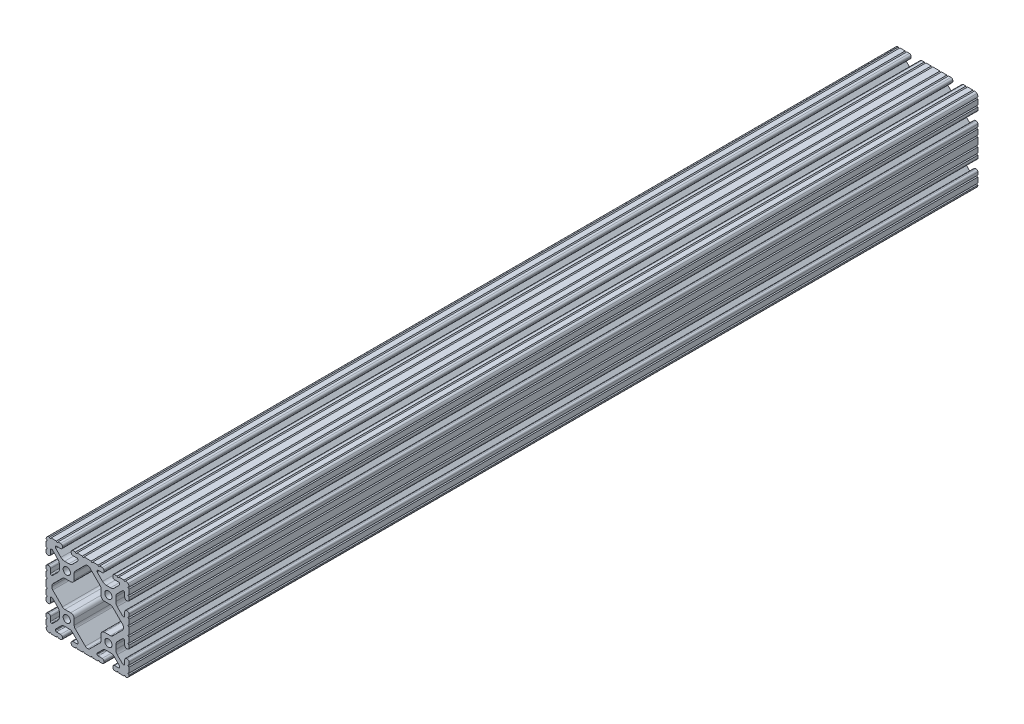
SolidWorks part; units mm, degrees
ref_plane "Front Plane" through (0, 0, 0) normal (0, 0, 1) x (1, 0, 0)
ref_plane "Top Plane" through (0, 0, 0) normal (0, 1, 0) x (1, 0, 0)
ref_plane "Right Plane" through (0, 0, 0) normal (1, 0, 0) x (0, 0, -1)
sketch "Sketch1" plane through (0, 0, 0) normal (0, 0, 1) x (1, 0, 0)
  line L0 (0, 38.1) -> (0, -38.1) construction
  line L1 (-38.1, -38.1) -> (38.1, -38.1) construction
  line L2 (-38.1, -38.1) -> (-38.1, 38.1) construction
  line L3 (-38.1, 38.1) -> (38.1, 38.1) construction
  line L4 (38.1, -38.1) -> (38.1, 38.1) construction
  line L5 (0, 38.1) -> (0, -38.1) construction
  line L6 (-38.1, 0) -> (38.1, 0) construction
  line L7 (-19.05, 19.05) -> (19.05, 19.05) construction
  line L8 (-19.05, 19.05) -> (-19.05, -19.05) construction
  line L9 (-19.05, -19.05) -> (19.05, -19.05) construction
  line L10 (19.05, 19.05) -> (19.05, -19.05) construction
  line L11 (-23.114, 38.1) -> (-23.114, -38.1) construction
  line L12 (-23.114, -38.1) -> (-14.986, 38.1) construction
  line L13 (-14.986, 38.1) -> (-14.986, -38.1) construction
  circle A0 centre (19.05, 19.05) radius 3.3274
  point P0 (0, 0)
  point P9 (0, 0)
  point P12 (-19.05, 0)
  line B0 (-11.3637, -22.8433) -> (-2.0515, -32.1555)
  line B1 (-12.2936, -15.4686) -> (-12.2936, -20.5983)
  line B2 (-20.769, -12.2936) -> (-15.4686, -12.2936)
  line B3 (-31.9021, -2.4756) -> (-23.0141, -11.3637)
  line B4 (-23.0141, 11.3637) -> (-31.9021, 2.4756)
  line B5 (-15.4686, 12.2936) -> (-20.769, 12.2936)
  line B6 (-12.2936, 20.5983) -> (-12.2936, 15.4686)
  line B7 (-2.0515, 32.1555) -> (-11.3637, 22.8433)
  line B8 (11.3637, 22.8433) -> (2.0515, 32.1555)
  line B9 (12.2936, 15.4686) -> (12.2936, 20.5983)
  line B10 (20.769, 12.2936) -> (15.4686, 12.2936)
  line B11 (31.9021, 2.4756) -> (23.0141, 11.3637)
  line B12 (23.0141, -11.3637) -> (31.9021, -2.4756)
  line B13 (15.4686, -12.2936) -> (20.769, -12.2936)
  line B14 (12.2936, -20.5983) -> (12.2936, -15.4686)
  line B15 (2.0515, -32.1555) -> (11.3637, -22.8433)
  line B16 (-4.7773, 38.1) -> (-9.6053, 38.1)
  line B17 (-11.1289, 38.1) -> (-13.4112, 38.1)
  line B18 (-14.986, 36.5252) -> (-14.986, 35.6108)
  line B19 (-13.4112, 34.036) -> (-9.652, 34.036)
  line B20 (-8.763, 33.147) -> (-8.763, 32.4935)
  line B21 (-9.0234, 31.8649) -> (-13.6907, 27.1976)
  line B22 (-17.0493, 25.8064) -> (-21.0507, 25.8064)
  line B23 (-24.4093, 27.1976) -> (-29.1002, 31.8885)
  line B24 (-29.337, 32.7207) -> (-29.337, 33.147)
  line B25 (-28.448, 34.036) -> (-24.6888, 34.036)
  line B26 (-23.114, 35.6108) -> (-23.114, 36.5252)
  line B27 (-24.6888, 38.1) -> (-27.0772, 38.1)
  line B28 (-28.6011, 38.1) -> (-33.4288, 38.1)
  line B29 (-38.1, 33.373) -> (-38.1, 28.5453)
  line B30 (-38.1, 27.0238) -> (-38.1, 24.6302)
  line B31 (-36.5252, 23.0554) -> (-35.6108, 23.0554)
  line B32 (-34.036, 24.6302) -> (-34.036, 28.448)
  line B33 (-33.147, 29.337) -> (-32.6643, 29.337)
  line B34 (-32.0357, 29.0766) -> (-27.1976, 24.2385)
  line B35 (-25.8064, 20.8799) -> (-25.8064, 17.2201)
  line B36 (-27.1976, 13.8615) -> (-31.9489, 9.1101)
  line B37 (-32.7869, 8.763) -> (-33.0603, 8.763)
  line B38 (-34.036, 9.7387) -> (-34.036, 13.4698)
  line B39 (-35.6108, 15.0446) -> (-36.5252, 15.0446)
  line B40 (-38.1, 13.4698) -> (-38.1, 11.075)
  line B41 (-38.1, 9.552) -> (-38.1, 4.7238)
  line B42 (-38.1, 3.2007) -> (-38.1, -3.2007)
  line B43 (-38.1, -4.7238) -> (-38.1, -9.552)
  line B44 (-38.1, -11.075) -> (-38.1, -13.4698)
  line B45 (-36.5252, -15.0446) -> (-35.6108, -15.0446)
  line B46 (-34.036, -13.4698) -> (-34.036, -9.7387)
  line B47 (-33.0603, -8.763) -> (-32.7869, -8.763)
  line B48 (-31.9489, -9.1101) -> (-27.1976, -13.8615)
  line B49 (-25.8064, -17.2201) -> (-25.8064, -20.8799)
  line B50 (-27.1976, -24.2385) -> (-32.0357, -29.0766)
  line B51 (-32.6643, -29.337) -> (-33.147, -29.337)
  line B52 (-34.036, -28.448) -> (-34.036, -24.6302)
  line B53 (-35.6108, -23.0554) -> (-36.5252, -23.0554)
  line B54 (-38.1, -24.6302) -> (-38.1, -27.0238)
  line B55 (-38.1, -28.5453) -> (-38.1, -33.373)
  line B56 (-33.4288, -38.1) -> (-28.6011, -38.1)
  line B57 (-27.0772, -38.1) -> (-24.6888, -38.1)
  line B58 (-23.114, -36.5252) -> (-23.114, -35.6108)
  line B59 (-24.6888, -34.036) -> (-28.448, -34.036)
  line B60 (-29.337, -33.147) -> (-29.337, -32.7207)
  line B61 (-29.1002, -31.8885) -> (-24.4093, -27.1976)
  line B62 (-21.0507, -25.8064) -> (-17.0493, -25.8064)
  line B63 (-13.6907, -27.1976) -> (-9.0234, -31.8649)
  line B64 (-8.763, -32.4935) -> (-8.763, -33.147)
  line B65 (-9.652, -34.036) -> (-13.4112, -34.036)
  line B66 (-14.986, -35.6108) -> (-14.986, -36.5252)
  line B67 (-13.4112, -38.1) -> (-11.1289, -38.1)
  line B68 (-9.6053, -38.1) -> (-4.7773, -38.1)
  line B69 (-3.2537, -38.1) -> (3.2537, -38.1)
  line B70 (4.7773, -38.1) -> (9.6053, -38.1)
  line B71 (11.1289, -38.1) -> (13.4112, -38.1)
  line B72 (14.986, -36.5252) -> (14.986, -35.6108)
  line B73 (13.4112, -34.036) -> (9.652, -34.036)
  line B74 (8.763, -33.147) -> (8.763, -32.4935)
  line B75 (9.0234, -31.8649) -> (13.6907, -27.1976)
  line B76 (17.0493, -25.8064) -> (21.0507, -25.8064)
  line B77 (24.4093, -27.1976) -> (29.1002, -31.8885)
  line B78 (29.337, -32.7207) -> (29.337, -33.147)
  line B79 (28.448, -34.036) -> (24.6888, -34.036)
  line B80 (23.114, -35.6108) -> (23.114, -36.5252)
  line B81 (24.6888, -38.1) -> (27.0772, -38.1)
  line B82 (28.6011, -38.1) -> (33.4288, -38.1)
  line B83 (38.1, -33.373) -> (38.1, -28.5453)
  line B84 (38.1, -27.0238) -> (38.1, -24.6302)
  line B85 (36.5252, -23.0554) -> (35.6108, -23.0554)
  line B86 (34.036, -24.6302) -> (34.036, -28.448)
  line B87 (33.147, -29.337) -> (32.6643, -29.337)
  line B88 (32.0357, -29.0766) -> (27.1976, -24.2385)
  line B89 (25.8064, -20.8799) -> (25.8064, -17.2201)
  line B90 (27.1976, -13.8615) -> (31.9489, -9.1101)
  line B91 (32.7869, -8.763) -> (33.0603, -8.763)
  line B92 (34.036, -9.7387) -> (34.036, -13.4698)
  line B93 (35.6108, -15.0446) -> (36.5252, -15.0446)
  line B94 (38.1, -13.4698) -> (38.1, -11.075)
  line B95 (38.1, -9.552) -> (38.1, -4.7238)
  line B96 (38.1, -3.2007) -> (38.1, 3.2007)
  line B97 (38.1, 4.7238) -> (38.1, 9.552)
  line B98 (38.1, 11.075) -> (38.1, 13.4698)
  line B99 (36.5252, 15.0446) -> (35.6108, 15.0446)
  line B100 (34.036, 13.4698) -> (34.036, 9.7387)
  line B101 (33.0603, 8.763) -> (32.7869, 8.763)
  line B102 (31.9489, 9.1101) -> (27.1976, 13.8615)
  line B103 (25.8064, 17.2201) -> (25.8064, 20.8799)
  line B104 (27.1976, 24.2385) -> (32.0357, 29.0766)
  line B105 (32.6643, 29.337) -> (33.147, 29.337)
  line B106 (34.036, 28.448) -> (34.036, 24.6302)
  line B107 (35.6108, 23.0554) -> (36.5252, 23.0554)
  line B108 (38.1, 24.6302) -> (38.1, 27.0238)
  line B109 (38.1, 28.5453) -> (38.1, 33.373)
  line B110 (33.4288, 38.1) -> (28.6011, 38.1)
  line B111 (27.0772, 38.1) -> (24.6888, 38.1)
  line B112 (23.114, 36.5252) -> (23.114, 35.6108)
  line B113 (24.6888, 34.036) -> (28.448, 34.036)
  line B114 (29.337, 33.147) -> (29.337, 32.7207)
  line B115 (29.1002, 31.8885) -> (24.4093, 27.1976)
  line B116 (21.0507, 25.8064) -> (17.0493, 25.8064)
  line B117 (13.6907, 27.1976) -> (9.0234, 31.8649)
  line B118 (8.763, 32.4935) -> (8.763, 33.147)
  line B119 (9.652, 34.036) -> (13.4112, 34.036)
  line B120 (14.986, 35.6108) -> (14.986, 36.5252)
  line B121 (13.4112, 38.1) -> (11.1289, 38.1)
  line B122 (9.6053, 38.1) -> (4.7773, 38.1)
  line B123 (3.2537, 38.1) -> (-3.2537, 38.1)
  circle B124 centre (-19.05, 19.05) radius 3.3274
  circle B125 centre (-19.05, -19.05) radius 3.3274
  circle B126 centre (19.05, -19.05) radius 3.3274
  circle B127 centre (19.05, 19.05) radius 3.3274
  arc B128 (0, -33.011) -> (2.0515, -32.1555) centre (-0.0139, -30.09) ccw
  arc B129 (-2.0515, -32.1555) -> (0, -33.011) centre (0.0139, -30.09) ccw
  arc B130 (-12.2936, -20.5983) -> (-11.3637, -22.8433) centre (-9.1186, -20.5983) ccw
  arc B131 (-12.2936, -15.4686) -> (-15.4686, -12.2936) centre (-15.4686, -15.4686) ccw
  arc B132 (-23.0141, -11.3637) -> (-20.769, -12.2936) centre (-20.769, -9.1186) ccw
  arc B133 (-32.7287, 0) -> (-31.9021, -2.4756) centre (-29.8367, -0.4102) ccw
  arc B134 (-31.9021, 2.4756) -> (-32.7287, 0) centre (-29.8367, 0.4102) ccw
  arc B135 (-20.769, 12.2936) -> (-23.0141, 11.3637) centre (-20.769, 9.1186) ccw
  arc B136 (-15.4686, 12.2936) -> (-12.2936, 15.4686) centre (-15.4686, 15.4686) ccw
  arc B137 (-11.3637, 22.8433) -> (-12.2936, 20.5983) centre (-9.1186, 20.5983) ccw
  arc B138 (0, 33.011) -> (-2.0515, 32.1555) centre (0.0139, 30.09) ccw
  arc B139 (2.0515, 32.1555) -> (0, 33.011) centre (-0.0139, 30.09) ccw
  arc B140 (12.2936, 20.5983) -> (11.3637, 22.8433) centre (9.1186, 20.5983) ccw
  arc B141 (12.2936, 15.4686) -> (15.4686, 12.2936) centre (15.4686, 15.4686) ccw
  arc B142 (23.0141, 11.3637) -> (20.769, 12.2936) centre (20.769, 9.1186) ccw
  arc B143 (32.7287, 0) -> (31.9021, 2.4756) centre (29.8367, 0.4102) ccw
  arc B144 (31.9021, -2.4756) -> (32.7287, 0) centre (29.8367, -0.4102) ccw
  arc B145 (20.769, -12.2936) -> (23.0141, -11.3637) centre (20.769, -9.1186) ccw
  arc B146 (15.4686, -12.2936) -> (12.2936, -15.4686) centre (15.4686, -15.4686) ccw
  arc B147 (11.3637, -22.8433) -> (12.2936, -20.5983) centre (9.1186, -20.5983) ccw
  arc B148 (-4.7773, 38.1) -> (-3.2537, 38.1) centre (-4.0155, 38.0824) ccw
  arc B149 (-11.1289, 38.1) -> (-9.6053, 38.1) centre (-10.3671, 38.0824) ccw
  arc B150 (-13.4112, 38.1) -> (-14.986, 36.5252) centre (-13.4112, 36.5252) ccw
  arc B151 (-14.986, 35.6108) -> (-13.4112, 34.036) centre (-13.4112, 35.6108) ccw
  arc B152 (-8.763, 33.147) -> (-9.652, 34.036) centre (-9.652, 33.147) ccw
  arc B153 (-9.0234, 31.8649) -> (-8.763, 32.4935) centre (-9.652, 32.4935) ccw
  arc B154 (-17.0493, 25.8064) -> (-13.6907, 27.1976) centre (-17.0493, 30.5562) ccw
  arc B155 (-24.4093, 27.1976) -> (-21.0507, 25.8064) centre (-21.0507, 30.5562) ccw
  arc B156 (-29.337, 32.7207) -> (-29.1002, 31.8885) centre (-28.4716, 32.5172) ccw
  arc B157 (-28.448, 34.036) -> (-29.337, 33.147) centre (-28.448, 33.147) ccw
  arc B158 (-24.6888, 34.036) -> (-23.114, 35.6108) centre (-24.6888, 35.6108) ccw
  arc B159 (-23.114, 36.5252) -> (-24.6888, 38.1) centre (-24.6888, 36.5252) ccw
  arc B160 (-28.6011, 38.1) -> (-27.0772, 38.1) centre (-27.8392, 38.0824) ccw
  arc B161 (-34.9527, 38.1) -> (-33.4288, 38.1) centre (-34.1907, 38.0824) ccw
  arc B162 (-34.9527, 38.1) -> (-37.0861, 37.1826) centre (-34.8521, 34.9266) ccw
  arc B163 (-37.0861, 37.1826) -> (-38.1, 34.8455) centre (-34.925, 34.8566) ccw
  arc B164 (-38.1, 33.373) -> (-38.1, 34.8455) centre (-37.9035, 34.1092) ccw
  arc B165 (-38.1, 27.0238) -> (-38.1, 28.5453) centre (-37.9035, 27.7845) ccw
  arc B166 (-38.1, 24.6302) -> (-36.5252, 23.0554) centre (-36.5252, 24.6302) ccw
  arc B167 (-35.6108, 23.0554) -> (-34.036, 24.6302) centre (-35.6108, 24.6302) ccw
  arc B168 (-33.147, 29.337) -> (-34.036, 28.448) centre (-33.147, 28.448) ccw
  arc B169 (-32.0357, 29.0766) -> (-32.6643, 29.337) centre (-32.6643, 28.448) ccw
  arc B170 (-25.8064, 20.8799) -> (-27.1976, 24.2385) centre (-30.5562, 20.8799) ccw
  arc B171 (-27.1976, 13.8615) -> (-25.8064, 17.2201) centre (-30.5562, 17.2201) ccw
  arc B172 (-32.7869, 8.763) -> (-31.9489, 9.1101) centre (-32.7869, 9.9481) ccw
  arc B173 (-34.036, 9.7387) -> (-33.0603, 8.763) centre (-33.0603, 9.7387) ccw
  arc B174 (-34.036, 13.4698) -> (-35.6108, 15.0446) centre (-35.6108, 13.4698) ccw
  arc B175 (-36.5252, 15.0446) -> (-38.1, 13.4698) centre (-36.5252, 13.4698) ccw
  arc B176 (-38.1, 9.552) -> (-38.1, 11.075) centre (-37.9035, 10.3135) ccw
  arc B177 (-38.1, 3.2007) -> (-38.1, 4.7238) centre (-37.9035, 3.9622) ccw
  arc B178 (-38.1, -4.7238) -> (-38.1, -3.2007) centre (-37.9035, -3.9622) ccw
  arc B179 (-38.1, -11.075) -> (-38.1, -9.552) centre (-37.9035, -10.3135) ccw
  arc B180 (-38.1, -13.4698) -> (-36.5252, -15.0446) centre (-36.5252, -13.4698) ccw
  arc B181 (-35.6108, -15.0446) -> (-34.036, -13.4698) centre (-35.6108, -13.4698) ccw
  arc B182 (-33.0603, -8.763) -> (-34.036, -9.7387) centre (-33.0603, -9.7387) ccw
  arc B183 (-31.9489, -9.1101) -> (-32.7869, -8.763) centre (-32.7869, -9.9481) ccw
  arc B184 (-25.8064, -17.2201) -> (-27.1976, -13.8615) centre (-30.5562, -17.2201) ccw
  arc B185 (-27.1976, -24.2385) -> (-25.8064, -20.8799) centre (-30.5562, -20.8799) ccw
  arc B186 (-32.6643, -29.337) -> (-32.0357, -29.0766) centre (-32.6643, -28.448) ccw
  arc B187 (-34.036, -28.448) -> (-33.147, -29.337) centre (-33.147, -28.448) ccw
  arc B188 (-34.036, -24.6302) -> (-35.6108, -23.0554) centre (-35.6108, -24.6302) ccw
  arc B189 (-36.5252, -23.0554) -> (-38.1, -24.6302) centre (-36.5252, -24.6302) ccw
  arc B190 (-38.1, -28.5453) -> (-38.1, -27.0238) centre (-37.9035, -27.7845) ccw
  arc B191 (-38.1, -34.8455) -> (-38.1, -33.373) centre (-37.9035, -34.1092) ccw
  arc B192 (-38.1, -34.8455) -> (-37.0861, -37.1826) centre (-34.925, -34.8566) ccw
  arc B193 (-37.0861, -37.1826) -> (-34.9527, -38.1) centre (-34.8521, -34.9266) ccw
  arc B194 (-33.4288, -38.1) -> (-34.9527, -38.1) centre (-34.1907, -38.0824) ccw
  arc B195 (-27.0772, -38.1) -> (-28.6011, -38.1) centre (-27.8392, -38.0824) ccw
  arc B196 (-24.6888, -38.1) -> (-23.114, -36.5252) centre (-24.6888, -36.5252) ccw
  arc B197 (-23.114, -35.6108) -> (-24.6888, -34.036) centre (-24.6888, -35.6108) ccw
  arc B198 (-29.337, -33.147) -> (-28.448, -34.036) centre (-28.448, -33.147) ccw
  arc B199 (-29.1002, -31.8885) -> (-29.337, -32.7207) centre (-28.4716, -32.5172) ccw
  arc B200 (-21.0507, -25.8064) -> (-24.4093, -27.1976) centre (-21.0507, -30.5562) ccw
  arc B201 (-13.6907, -27.1976) -> (-17.0493, -25.8064) centre (-17.0493, -30.5562) ccw
  arc B202 (-8.763, -32.4935) -> (-9.0234, -31.8649) centre (-9.652, -32.4935) ccw
  arc B203 (-9.652, -34.036) -> (-8.763, -33.147) centre (-9.652, -33.147) ccw
  arc B204 (-13.4112, -34.036) -> (-14.986, -35.6108) centre (-13.4112, -35.6108) ccw
  arc B205 (-14.986, -36.5252) -> (-13.4112, -38.1) centre (-13.4112, -36.5252) ccw
  arc B206 (-9.6053, -38.1) -> (-11.1289, -38.1) centre (-10.3671, -38.0824) ccw
  arc B207 (-3.2537, -38.1) -> (-4.7773, -38.1) centre (-4.0155, -38.0824) ccw
  arc B208 (4.7773, -38.1) -> (3.2537, -38.1) centre (4.0155, -38.0824) ccw
  arc B209 (11.1289, -38.1) -> (9.6053, -38.1) centre (10.3671, -38.0824) ccw
  arc B210 (13.4112, -38.1) -> (14.986, -36.5252) centre (13.4112, -36.5252) ccw
  arc B211 (14.986, -35.6108) -> (13.4112, -34.036) centre (13.4112, -35.6108) ccw
  arc B212 (8.763, -33.147) -> (9.652, -34.036) centre (9.652, -33.147) ccw
  arc B213 (9.0234, -31.8649) -> (8.763, -32.4935) centre (9.652, -32.4935) ccw
  arc B214 (17.0493, -25.8064) -> (13.6907, -27.1976) centre (17.0493, -30.5562) ccw
  arc B215 (24.4093, -27.1976) -> (21.0507, -25.8064) centre (21.0507, -30.5562) ccw
  arc B216 (29.337, -32.7207) -> (29.1002, -31.8885) centre (28.4716, -32.5172) ccw
  arc B217 (28.448, -34.036) -> (29.337, -33.147) centre (28.448, -33.147) ccw
  arc B218 (24.6888, -34.036) -> (23.114, -35.6108) centre (24.6888, -35.6108) ccw
  arc B219 (23.114, -36.5252) -> (24.6888, -38.1) centre (24.6888, -36.5252) ccw
  arc B220 (28.6011, -38.1) -> (27.0772, -38.1) centre (27.8392, -38.0824) ccw
  arc B221 (34.9527, -38.1) -> (33.4288, -38.1) centre (34.1907, -38.0824) ccw
  arc B222 (34.9527, -38.1) -> (37.0861, -37.1826) centre (34.8521, -34.9266) ccw
  arc B223 (37.0861, -37.1826) -> (38.1, -34.8455) centre (34.925, -34.8566) ccw
  arc B224 (38.1, -33.373) -> (38.1, -34.8455) centre (37.9035, -34.1092) ccw
  arc B225 (38.1, -27.0238) -> (38.1, -28.5453) centre (37.9035, -27.7845) ccw
  arc B226 (38.1, -24.6302) -> (36.5252, -23.0554) centre (36.5252, -24.6302) ccw
  arc B227 (35.6108, -23.0554) -> (34.036, -24.6302) centre (35.6108, -24.6302) ccw
  arc B228 (33.147, -29.337) -> (34.036, -28.448) centre (33.147, -28.448) ccw
  arc B229 (32.0357, -29.0766) -> (32.6643, -29.337) centre (32.6643, -28.448) ccw
  arc B230 (25.8064, -20.8799) -> (27.1976, -24.2385) centre (30.5562, -20.8799) ccw
  arc B231 (27.1976, -13.8615) -> (25.8064, -17.2201) centre (30.5562, -17.2201) ccw
  arc B232 (32.7869, -8.763) -> (31.9489, -9.1101) centre (32.7869, -9.9481) ccw
  arc B233 (34.036, -9.7387) -> (33.0603, -8.763) centre (33.0603, -9.7387) ccw
  arc B234 (34.036, -13.4698) -> (35.6108, -15.0446) centre (35.6108, -13.4698) ccw
  arc B235 (36.5252, -15.0446) -> (38.1, -13.4698) centre (36.5252, -13.4698) ccw
  arc B236 (38.1, -9.552) -> (38.1, -11.075) centre (37.9035, -10.3135) ccw
  arc B237 (38.1, -3.2007) -> (38.1, -4.7238) centre (37.9035, -3.9622) ccw
  arc B238 (38.1, 4.7238) -> (38.1, 3.2007) centre (37.9035, 3.9622) ccw
  arc B239 (38.1, 11.075) -> (38.1, 9.552) centre (37.9035, 10.3135) ccw
  arc B240 (38.1, 13.4698) -> (36.5252, 15.0446) centre (36.5252, 13.4698) ccw
  arc B241 (35.6108, 15.0446) -> (34.036, 13.4698) centre (35.6108, 13.4698) ccw
  arc B242 (33.0603, 8.763) -> (34.036, 9.7387) centre (33.0603, 9.7387) ccw
  arc B243 (31.9489, 9.1101) -> (32.7869, 8.763) centre (32.7869, 9.9481) ccw
  arc B244 (25.8064, 17.2201) -> (27.1976, 13.8615) centre (30.5562, 17.2201) ccw
  arc B245 (27.1976, 24.2385) -> (25.8064, 20.8799) centre (30.5562, 20.8799) ccw
  arc B246 (32.6643, 29.337) -> (32.0357, 29.0766) centre (32.6643, 28.448) ccw
  arc B247 (34.036, 28.448) -> (33.147, 29.337) centre (33.147, 28.448) ccw
  arc B248 (34.036, 24.6302) -> (35.6108, 23.0554) centre (35.6108, 24.6302) ccw
  arc B249 (36.5252, 23.0554) -> (38.1, 24.6302) centre (36.5252, 24.6302) ccw
  arc B250 (38.1, 28.5453) -> (38.1, 27.0238) centre (37.9035, 27.7845) ccw
  arc B251 (38.1, 34.8455) -> (38.1, 33.373) centre (37.9035, 34.1092) ccw
  arc B252 (38.1, 34.8455) -> (37.0861, 37.1826) centre (34.925, 34.8566) ccw
  arc B253 (37.0861, 37.1826) -> (34.9527, 38.1) centre (34.8521, 34.9266) ccw
  arc B254 (33.4288, 38.1) -> (34.9527, 38.1) centre (34.1907, 38.0824) ccw
  arc B255 (27.0772, 38.1) -> (28.6011, 38.1) centre (27.8392, 38.0824) ccw
  arc B256 (24.6888, 38.1) -> (23.114, 36.5252) centre (24.6888, 36.5252) ccw
  arc B257 (23.114, 35.6108) -> (24.6888, 34.036) centre (24.6888, 35.6108) ccw
  arc B258 (29.337, 33.147) -> (28.448, 34.036) centre (28.448, 33.147) ccw
  arc B259 (29.1002, 31.8885) -> (29.337, 32.7207) centre (28.4716, 32.5172) ccw
  arc B260 (21.0507, 25.8064) -> (24.4093, 27.1976) centre (21.0507, 30.5562) ccw
  arc B261 (13.6907, 27.1976) -> (17.0493, 25.8064) centre (17.0493, 30.5562) ccw
  arc B262 (8.763, 32.4935) -> (9.0234, 31.8649) centre (9.652, 32.4935) ccw
  arc B263 (9.652, 34.036) -> (8.763, 33.147) centre (9.652, 33.147) ccw
  arc B264 (13.4112, 34.036) -> (14.986, 35.6108) centre (13.4112, 35.6108) ccw
  arc B265 (14.986, 36.5252) -> (13.4112, 38.1) centre (13.4112, 36.5252) ccw
  arc B266 (9.6053, 38.1) -> (11.1289, 38.1) centre (10.3671, 38.0824) ccw
  arc B267 (3.2537, 38.1) -> (4.7773, 38.1) centre (4.0155, 38.0824) ccw
  dimension "Center Hole Diameter" = 6.6548
  dimension "Rail Width" = 76.2
  dimension "Rail Height" = 76.2
  dimension "T-Slot Width" = 8.128
sketch_block_instance "Block1-1"
sketch_block "Block1"
sketch "Sketch2" plane through (0, 0, 0) normal (1, 0, 0) x (0, 0, -1)
  line L0 (-388.8, 0) -> (388.8, 0) construction
  line L1 (-388.8, 38.1) -> (-388.8, -38.1) construction
  line L2 (-388.8, -38.1) -> (388.8, -38.1) construction
  line L3 (388.8, -38.1) -> (388.8, 38.1) construction
  line L4 (-287.2, 0) -> (-287.2, 38.1) construction
  line L5 (-287.2, 38.1) -> (287.2, 38.1) construction
  line L6 (287.2, 38.1) -> (287.2, 0) construction
  point P5 (287.2, 0)
  point P10 (-287.2, 0)
  dimension "D1" = 101.6
  dimension "Length" = 777.6
  dimension "D2" = 101.6
sketch "Sketch3" plane through (0, 0, 0) normal (0, 0, 1) x (1, 0, 0)
  line L0 (-11.3637, -22.8433) -> (-2.0515, -32.1555) construction
  line L1 (-12.2936, -15.4686) -> (-12.2936, -20.5983) construction
  line L2 (-20.769, -12.2936) -> (-15.4686, -12.2936) construction
  line L3 (-31.9021, -2.4756) -> (-23.0141, -11.3637) construction
  line L4 (-23.0141, 11.3637) -> (-31.9021, 2.4756) construction
  line L5 (-15.4686, 12.2936) -> (-20.769, 12.2936) construction
  line L6 (-12.2936, 20.5983) -> (-12.2936, 15.4686) construction
  line L7 (-2.0515, 32.1555) -> (-11.3637, 22.8433) construction
  line L8 (11.3637, 22.8433) -> (2.0515, 32.1555) construction
  line L9 (12.2936, 15.4686) -> (12.2936, 20.5983) construction
  line L10 (20.769, 12.2936) -> (15.4686, 12.2936) construction
  line L11 (31.9021, 2.4756) -> (23.0141, 11.3637) construction
  line L12 (23.0141, -11.3637) -> (31.9021, -2.4756) construction
  line L13 (15.4686, -12.2936) -> (20.769, -12.2936) construction
  line L14 (12.2936, -20.5983) -> (12.2936, -15.4686) construction
  line L15 (2.0515, -32.1555) -> (11.3637, -22.8433) construction
  line L16 (34.036, 28.448) -> (34.036, 24.6302) construction
  line L17 (35.6108, 23.0554) -> (36.5252, 23.0554) construction
  line L18 (38.1, 24.6302) -> (38.1, 27.0238) construction
  line L19 (38.1, 28.5453) -> (38.1, 33.373) construction
  line L20 (33.4288, 38.1) -> (28.6011, 38.1) construction
  line L21 (27.0772, 38.1) -> (24.6888, 38.1) construction
  line L22 (23.114, 36.5252) -> (23.114, 35.6108) construction
  line L23 (24.6888, 34.036) -> (28.448, 34.036) construction
  line L24 (29.337, 33.147) -> (29.337, 32.7207) construction
  line L25 (29.1002, 31.8885) -> (24.4093, 27.1976) construction
  line L26 (21.0507, 25.8064) -> (17.0493, 25.8064) construction
  line L27 (13.6907, 27.1976) -> (9.0234, 31.8649) construction
  line L28 (8.763, 32.4935) -> (8.763, 33.147) construction
  line L29 (9.652, 34.036) -> (13.4112, 34.036) construction
  line L30 (14.986, 35.6108) -> (14.986, 36.5252) construction
  line L31 (13.4112, 38.1) -> (11.1289, 38.1) construction
  line L32 (9.6053, 38.1) -> (4.7773, 38.1) construction
  line L33 (3.2537, 38.1) -> (-3.2537, 38.1) construction
  line L34 (-4.7773, 38.1) -> (-9.6053, 38.1) construction
  line L35 (-11.1289, 38.1) -> (-13.4112, 38.1) construction
  line L36 (-14.986, 36.5252) -> (-14.986, 35.6108) construction
  line L37 (-13.4112, 34.036) -> (-9.652, 34.036) construction
  line L38 (-8.763, 33.147) -> (-8.763, 32.4935) construction
  line L39 (-9.0234, 31.8649) -> (-13.6907, 27.1976) construction
  line L40 (-17.0493, 25.8064) -> (-21.0507, 25.8064) construction
  line L41 (-24.4093, 27.1976) -> (-29.1002, 31.8885) construction
  line L42 (-29.337, 32.7207) -> (-29.337, 33.147) construction
  line L43 (-28.448, 34.036) -> (-24.6888, 34.036) construction
  line L44 (-23.114, 35.6108) -> (-23.114, 36.5252) construction
  line L45 (-24.6888, 38.1) -> (-27.0772, 38.1) construction
  line L46 (-28.6011, 38.1) -> (-33.4288, 38.1) construction
  line L47 (-38.1, 33.373) -> (-38.1, 28.5453) construction
  line L48 (-38.1, 27.0238) -> (-38.1, 24.6302) construction
  line L49 (-36.5252, 23.0554) -> (-35.6108, 23.0554) construction
  line L50 (-34.036, 24.6302) -> (-34.036, 28.448) construction
  line L51 (-33.147, 29.337) -> (-32.6643, 29.337) construction
  line L52 (-32.0357, 29.0766) -> (-27.1976, 24.2385) construction
  line L53 (-25.8064, 20.8799) -> (-25.8064, 17.2201) construction
  line L54 (-27.1976, 13.8615) -> (-31.9489, 9.1101) construction
  line L55 (-32.7869, 8.763) -> (-33.0603, 8.763) construction
  line L56 (-34.036, 9.7387) -> (-34.036, 13.4698) construction
  line L57 (-35.6108, 15.0446) -> (-36.5252, 15.0446) construction
  line L58 (-38.1, 13.4698) -> (-38.1, 11.075) construction
  line L59 (-38.1, 9.552) -> (-38.1, 4.7238) construction
  line L60 (-38.1, 3.2007) -> (-38.1, -3.2007) construction
  line L61 (-38.1, -4.7238) -> (-38.1, -9.552) construction
  line L62 (-38.1, -11.075) -> (-38.1, -13.4698) construction
  line L63 (-36.5252, -15.0446) -> (-35.6108, -15.0446) construction
  line L64 (-34.036, -13.4698) -> (-34.036, -9.7387) construction
  line L65 (-33.0603, -8.763) -> (-32.7869, -8.763) construction
  line L66 (-31.9489, -9.1101) -> (-27.1976, -13.8615) construction
  line L67 (-25.8064, -17.2201) -> (-25.8064, -20.8799) construction
  line L68 (-27.1976, -24.2385) -> (-32.0357, -29.0766) construction
  line L69 (-32.6643, -29.337) -> (-33.147, -29.337) construction
  line L70 (-34.036, -28.448) -> (-34.036, -24.6302) construction
  line L71 (-35.6108, -23.0554) -> (-36.5252, -23.0554) construction
  line L72 (-38.1, -24.6302) -> (-38.1, -27.0238) construction
  line L73 (-38.1, -28.5453) -> (-38.1, -33.373) construction
  line L74 (-33.4288, -38.1) -> (-28.6011, -38.1) construction
  line L75 (-27.0772, -38.1) -> (-24.6888, -38.1) construction
  line L76 (-23.114, -36.5252) -> (-23.114, -35.6108) construction
  line L77 (-24.6888, -34.036) -> (-28.448, -34.036) construction
  line L78 (-29.337, -33.147) -> (-29.337, -32.7207) construction
  line L79 (-29.1002, -31.8885) -> (-24.4093, -27.1976) construction
  line L80 (-21.0507, -25.8064) -> (-17.0493, -25.8064) construction
  line L81 (-13.6907, -27.1976) -> (-9.0234, -31.8649) construction
  line L82 (-8.763, -32.4935) -> (-8.763, -33.147) construction
  line L83 (-9.652, -34.036) -> (-13.4112, -34.036) construction
  line L84 (-14.986, -35.6108) -> (-14.986, -36.5252) construction
  line L85 (-13.4112, -38.1) -> (-11.1289, -38.1) construction
  line L86 (-9.6053, -38.1) -> (-4.7773, -38.1) construction
  line L87 (-3.2537, -38.1) -> (3.2537, -38.1) construction
  line L88 (4.7773, -38.1) -> (9.6053, -38.1) construction
  line L89 (11.1289, -38.1) -> (13.4112, -38.1) construction
  line L90 (14.986, -36.5252) -> (14.986, -35.6108) construction
  line L91 (13.4112, -34.036) -> (9.652, -34.036) construction
  line L92 (8.763, -33.147) -> (8.763, -32.4935) construction
  line L93 (9.0234, -31.8649) -> (13.6907, -27.1976) construction
  line L94 (17.0493, -25.8064) -> (21.0507, -25.8064) construction
  line L95 (24.4093, -27.1976) -> (29.1002, -31.8885) construction
  line L96 (29.337, -32.7207) -> (29.337, -33.147) construction
  line L97 (28.448, -34.036) -> (24.6888, -34.036) construction
  line L98 (23.114, -35.6108) -> (23.114, -36.5252) construction
  line L99 (24.6888, -38.1) -> (27.0772, -38.1) construction
  line L100 (28.6011, -38.1) -> (33.4288, -38.1) construction
  line L101 (38.1, -33.373) -> (38.1, -28.5453) construction
  line L102 (38.1, -27.0238) -> (38.1, -24.6302) construction
  line L103 (36.5252, -23.0554) -> (35.6108, -23.0554) construction
  line L104 (34.036, -24.6302) -> (34.036, -28.448) construction
  line L105 (33.147, -29.337) -> (32.6643, -29.337) construction
  line L106 (32.0357, -29.0766) -> (27.1976, -24.2385) construction
  line L107 (25.8064, -20.8799) -> (25.8064, -17.2201) construction
  line L108 (27.1976, -13.8615) -> (31.9489, -9.1101) construction
  line L109 (32.7869, -8.763) -> (33.0603, -8.763) construction
  line L110 (34.036, -9.7387) -> (34.036, -13.4698) construction
  line L111 (35.6108, -15.0446) -> (36.5252, -15.0446) construction
  line L112 (38.1, -13.4698) -> (38.1, -11.075) construction
  line L113 (38.1, -9.552) -> (38.1, -4.7238) construction
  line L114 (38.1, -3.2007) -> (38.1, 3.2007) construction
  line L115 (38.1, 4.7238) -> (38.1, 9.552) construction
  line L116 (38.1, 11.075) -> (38.1, 13.4698) construction
  line L117 (36.5252, 15.0446) -> (35.6108, 15.0446) construction
  line L118 (34.036, 13.4698) -> (34.036, 9.7387) construction
  line L119 (33.0603, 8.763) -> (32.7869, 8.763) construction
  line L120 (31.9489, 9.1101) -> (27.1976, 13.8615) construction
  line L121 (25.8064, 17.2201) -> (25.8064, 20.8799) construction
  line L122 (27.1976, 24.2385) -> (32.0357, 29.0766) construction
  line L123 (32.6643, 29.337) -> (33.147, 29.337) construction
  line L124 (-11.3637, -22.8433) -> (-2.0515, -32.1555)
  line L125 (-12.2936, -15.4686) -> (-12.2936, -20.5983)
  line L126 (-20.769, -12.2936) -> (-15.4686, -12.2936)
  line L127 (-31.9021, -2.4756) -> (-23.0141, -11.3637)
  line L128 (-23.0141, 11.3637) -> (-31.9021, 2.4756)
  line L129 (-15.4686, 12.2936) -> (-20.769, 12.2936)
  line L130 (-12.2936, 20.5983) -> (-12.2936, 15.4686)
  line L131 (-2.0515, 32.1555) -> (-11.3637, 22.8433)
  line L132 (11.3637, 22.8433) -> (2.0515, 32.1555)
  line L133 (12.2936, 15.4686) -> (12.2936, 20.5983)
  line L134 (20.769, 12.2936) -> (15.4686, 12.2936)
  line L135 (31.9021, 2.4756) -> (23.0141, 11.3637)
  line L136 (23.0141, -11.3637) -> (31.9021, -2.4756)
  line L137 (15.4686, -12.2936) -> (20.769, -12.2936)
  line L138 (12.2936, -20.5983) -> (12.2936, -15.4686)
  line L139 (2.0515, -32.1555) -> (11.3637, -22.8433)
  line L140 (34.036, 28.448) -> (34.036, 24.6302)
  line L141 (35.6108, 23.0554) -> (36.5252, 23.0554)
  line L142 (38.1, 24.6302) -> (38.1, 27.0238)
  line L143 (38.1, 28.5453) -> (38.1, 33.373)
  line L144 (33.4288, 38.1) -> (28.6011, 38.1)
  line L145 (27.0772, 38.1) -> (24.6888, 38.1)
  line L146 (23.114, 36.5252) -> (23.114, 35.6108)
  line L147 (24.6888, 34.036) -> (28.448, 34.036)
  line L148 (29.337, 33.147) -> (29.337, 32.7207)
  line L149 (29.1002, 31.8885) -> (24.4093, 27.1976)
  line L150 (21.0507, 25.8064) -> (17.0493, 25.8064)
  line L151 (13.6907, 27.1976) -> (9.0234, 31.8649)
  line L152 (8.763, 32.4935) -> (8.763, 33.147)
  line L153 (9.652, 34.036) -> (13.4112, 34.036)
  line L154 (14.986, 35.6108) -> (14.986, 36.5252)
  line L155 (13.4112, 38.1) -> (11.1289, 38.1)
  line L156 (9.6053, 38.1) -> (4.7773, 38.1)
  line L157 (3.2537, 38.1) -> (-3.2537, 38.1)
  line L158 (-4.7773, 38.1) -> (-9.6053, 38.1)
  line L159 (-11.1289, 38.1) -> (-13.4112, 38.1)
  line L160 (-14.986, 36.5252) -> (-14.986, 35.6108)
  line L161 (-13.4112, 34.036) -> (-9.652, 34.036)
  line L162 (-8.763, 33.147) -> (-8.763, 32.4935)
  line L163 (-9.0234, 31.8649) -> (-13.6907, 27.1976)
  line L164 (-17.0493, 25.8064) -> (-21.0507, 25.8064)
  line L165 (-24.4093, 27.1976) -> (-29.1002, 31.8885)
  line L166 (-29.337, 32.7207) -> (-29.337, 33.147)
  line L167 (-28.448, 34.036) -> (-24.6888, 34.036)
  line L168 (-23.114, 35.6108) -> (-23.114, 36.5252)
  line L169 (-24.6888, 38.1) -> (-27.0772, 38.1)
  line L170 (-28.6011, 38.1) -> (-33.4288, 38.1)
  line L171 (-38.1, 33.373) -> (-38.1, 28.5453)
  line L172 (-38.1, 27.0238) -> (-38.1, 24.6302)
  line L173 (-36.5252, 23.0554) -> (-35.6108, 23.0554)
  line L174 (-34.036, 24.6302) -> (-34.036, 28.448)
  line L175 (-33.147, 29.337) -> (-32.6643, 29.337)
  line L176 (-32.0357, 29.0766) -> (-27.1976, 24.2385)
  line L177 (-25.8064, 20.8799) -> (-25.8064, 17.2201)
  line L178 (-27.1976, 13.8615) -> (-31.9489, 9.1101)
  line L179 (-32.7869, 8.763) -> (-33.0603, 8.763)
  line L180 (-34.036, 9.7387) -> (-34.036, 13.4698)
  line L181 (-35.6108, 15.0446) -> (-36.5252, 15.0446)
  line L182 (-38.1, 13.4698) -> (-38.1, 11.075)
  line L183 (-38.1, 9.552) -> (-38.1, 4.7238)
  line L184 (-38.1, 3.2007) -> (-38.1, -3.2007)
  line L185 (-38.1, -4.7238) -> (-38.1, -9.552)
  line L186 (-38.1, -11.075) -> (-38.1, -13.4698)
  line L187 (-36.5252, -15.0446) -> (-35.6108, -15.0446)
  line L188 (-34.036, -13.4698) -> (-34.036, -9.7387)
  line L189 (-33.0603, -8.763) -> (-32.7869, -8.763)
  line L190 (-31.9489, -9.1101) -> (-27.1976, -13.8615)
  line L191 (-25.8064, -17.2201) -> (-25.8064, -20.8799)
  line L192 (-27.1976, -24.2385) -> (-32.0357, -29.0766)
  line L193 (-32.6643, -29.337) -> (-33.147, -29.337)
  line L194 (-34.036, -28.448) -> (-34.036, -24.6302)
  line L195 (-35.6108, -23.0554) -> (-36.5252, -23.0554)
  line L196 (-38.1, -24.6302) -> (-38.1, -27.0238)
  line L197 (-38.1, -28.5453) -> (-38.1, -33.373)
  line L198 (-33.4288, -38.1) -> (-28.6011, -38.1)
  line L199 (-27.0772, -38.1) -> (-24.6888, -38.1)
  line L200 (-23.114, -36.5252) -> (-23.114, -35.6108)
  line L201 (-24.6888, -34.036) -> (-28.448, -34.036)
  line L202 (-29.337, -33.147) -> (-29.337, -32.7207)
  line L203 (-29.1002, -31.8885) -> (-24.4093, -27.1976)
  line L204 (-21.0507, -25.8064) -> (-17.0493, -25.8064)
  line L205 (-13.6907, -27.1976) -> (-9.0234, -31.8649)
  line L206 (-8.763, -32.4935) -> (-8.763, -33.147)
  line L207 (-9.652, -34.036) -> (-13.4112, -34.036)
  line L208 (-14.986, -35.6108) -> (-14.986, -36.5252)
  line L209 (-13.4112, -38.1) -> (-11.1289, -38.1)
  line L210 (-9.6053, -38.1) -> (-4.7773, -38.1)
  line L211 (-3.2537, -38.1) -> (3.2537, -38.1)
  line L212 (4.7773, -38.1) -> (9.6053, -38.1)
  line L213 (11.1289, -38.1) -> (13.4112, -38.1)
  line L214 (14.986, -36.5252) -> (14.986, -35.6108)
  line L215 (13.4112, -34.036) -> (9.652, -34.036)
  line L216 (8.763, -33.147) -> (8.763, -32.4935)
  line L217 (9.0234, -31.8649) -> (13.6907, -27.1976)
  line L218 (17.0493, -25.8064) -> (21.0507, -25.8064)
  line L219 (24.4093, -27.1976) -> (29.1002, -31.8885)
  line L220 (29.337, -32.7207) -> (29.337, -33.147)
  line L221 (28.448, -34.036) -> (24.6888, -34.036)
  line L222 (23.114, -35.6108) -> (23.114, -36.5252)
  line L223 (24.6888, -38.1) -> (27.0772, -38.1)
  line L224 (28.6011, -38.1) -> (33.4288, -38.1)
  line L225 (38.1, -33.373) -> (38.1, -28.5453)
  line L226 (38.1, -27.0238) -> (38.1, -24.6302)
  line L227 (36.5252, -23.0554) -> (35.6108, -23.0554)
  line L228 (34.036, -24.6302) -> (34.036, -28.448)
  line L229 (33.147, -29.337) -> (32.6643, -29.337)
  line L230 (32.0357, -29.0766) -> (27.1976, -24.2385)
  line L231 (25.8064, -20.8799) -> (25.8064, -17.2201)
  line L232 (27.1976, -13.8615) -> (31.9489, -9.1101)
  line L233 (32.7869, -8.763) -> (33.0603, -8.763)
  line L234 (34.036, -9.7387) -> (34.036, -13.4698)
  line L235 (35.6108, -15.0446) -> (36.5252, -15.0446)
  line L236 (38.1, -13.4698) -> (38.1, -11.075)
  line L237 (38.1, -9.552) -> (38.1, -4.7238)
  line L238 (38.1, -3.2007) -> (38.1, 3.2007)
  line L239 (38.1, 4.7238) -> (38.1, 9.552)
  line L240 (38.1, 11.075) -> (38.1, 13.4698)
  line L241 (36.5252, 15.0446) -> (35.6108, 15.0446)
  line L242 (34.036, 13.4698) -> (34.036, 9.7387)
  line L243 (33.0603, 8.763) -> (32.7869, 8.763)
  line L244 (31.9489, 9.1101) -> (27.1976, 13.8615)
  line L245 (25.8064, 17.2201) -> (25.8064, 20.8799)
  line L246 (27.1976, 24.2385) -> (32.0357, 29.0766)
  line L247 (32.6643, 29.337) -> (33.147, 29.337)
  arc A0 (-2.0515, -32.1555) -> (0, -33.011) centre (0.0139, -30.09) ccw construction
  circle A1 centre (19.05, 19.05) radius 3.3274
  circle A2 centre (19.05, 19.05) radius 3.3274
  arc A3 (-12.2936, -20.5983) -> (-11.3637, -22.8433) centre (-9.1186, -20.5983) ccw construction
  arc A4 (-12.2936, -15.4686) -> (-15.4686, -12.2936) centre (-15.4686, -15.4686) ccw construction
  arc A5 (-23.0141, -11.3637) -> (-20.769, -12.2936) centre (-20.769, -9.1186) ccw construction
  arc A6 (-32.7287, 0) -> (-31.9021, -2.4756) centre (-29.8367, -0.4102) ccw construction
  arc A7 (-31.9021, 2.4756) -> (-32.7287, 0) centre (-29.8367, 0.4102) ccw construction
  arc A8 (-20.769, 12.2936) -> (-23.0141, 11.3637) centre (-20.769, 9.1186) ccw construction
  arc A9 (-15.4686, 12.2936) -> (-12.2936, 15.4686) centre (-15.4686, 15.4686) ccw construction
  arc A10 (-11.3637, 22.8433) -> (-12.2936, 20.5983) centre (-9.1186, 20.5983) ccw construction
  arc A11 (0, 33.011) -> (-2.0515, 32.1555) centre (0.0139, 30.09) ccw construction
  arc A12 (2.0515, 32.1555) -> (0, 33.011) centre (-0.0139, 30.09) ccw construction
  arc A13 (12.2936, 20.5983) -> (11.3637, 22.8433) centre (9.1186, 20.5983) ccw construction
  arc A14 (12.2936, 15.4686) -> (15.4686, 12.2936) centre (15.4686, 15.4686) ccw construction
  arc A15 (23.0141, 11.3637) -> (20.769, 12.2936) centre (20.769, 9.1186) ccw construction
  arc A16 (32.7287, 0) -> (31.9021, 2.4756) centre (29.8367, 0.4102) ccw construction
  arc A17 (31.9021, -2.4756) -> (32.7287, 0) centre (29.8367, -0.4102) ccw construction
  arc A18 (20.769, -12.2936) -> (23.0141, -11.3637) centre (20.769, -9.1186) ccw construction
  arc A19 (15.4686, -12.2936) -> (12.2936, -15.4686) centre (15.4686, -15.4686) ccw construction
  arc A20 (11.3637, -22.8433) -> (12.2936, -20.5983) centre (9.1186, -20.5983) ccw construction
  arc A21 (0, -33.011) -> (2.0515, -32.1555) centre (-0.0139, -30.09) ccw construction
  circle A22 centre (-19.05, 19.05) radius 3.3274 construction
  circle A23 centre (19.05, -19.05) radius 3.3274 construction
  circle A24 centre (-19.05, -19.05) radius 3.3274 construction
  circle A25 centre (19.05, 19.05) radius 3.3274 construction
  arc A26 (34.036, 24.6302) -> (35.6108, 23.0554) centre (35.6108, 24.6302) ccw construction
  arc A27 (36.5252, 23.0554) -> (38.1, 24.6302) centre (36.5252, 24.6302) ccw construction
  arc A28 (38.1, 28.5453) -> (38.1, 27.0238) centre (37.9035, 27.7845) ccw construction
  arc A29 (38.1, 34.8455) -> (38.1, 33.373) centre (37.9035, 34.1092) ccw construction
  arc A30 (38.1, 34.8455) -> (37.0861, 37.1826) centre (34.925, 34.8566) ccw construction
  arc A31 (37.0861, 37.1826) -> (34.9527, 38.1) centre (34.8521, 34.9266) ccw construction
  arc A32 (33.4288, 38.1) -> (34.9527, 38.1) centre (34.1907, 38.0824) ccw construction
  arc A33 (27.0772, 38.1) -> (28.6011, 38.1) centre (27.8392, 38.0824) ccw construction
  arc A34 (24.6888, 38.1) -> (23.114, 36.5252) centre (24.6888, 36.5252) ccw construction
  arc A35 (23.114, 35.6108) -> (24.6888, 34.036) centre (24.6888, 35.6108) ccw construction
  arc A36 (29.337, 33.147) -> (28.448, 34.036) centre (28.448, 33.147) ccw construction
  arc A37 (29.1002, 31.8885) -> (29.337, 32.7207) centre (28.4716, 32.5172) ccw construction
  arc A38 (21.0507, 25.8064) -> (24.4093, 27.1976) centre (21.0507, 30.5562) ccw construction
  arc A39 (13.6907, 27.1976) -> (17.0493, 25.8064) centre (17.0493, 30.5562) ccw construction
  arc A40 (8.763, 32.4935) -> (9.0234, 31.8649) centre (9.652, 32.4935) ccw construction
  arc A41 (9.652, 34.036) -> (8.763, 33.147) centre (9.652, 33.147) ccw construction
  arc A42 (13.4112, 34.036) -> (14.986, 35.6108) centre (13.4112, 35.6108) ccw construction
  arc A43 (14.986, 36.5252) -> (13.4112, 38.1) centre (13.4112, 36.5252) ccw construction
  arc A44 (9.6053, 38.1) -> (11.1289, 38.1) centre (10.3671, 38.0824) ccw construction
  arc A45 (3.2537, 38.1) -> (4.7773, 38.1) centre (4.0155, 38.0824) ccw construction
  arc A46 (-4.7773, 38.1) -> (-3.2537, 38.1) centre (-4.0155, 38.0824) ccw construction
  arc A47 (-11.1289, 38.1) -> (-9.6053, 38.1) centre (-10.3671, 38.0824) ccw construction
  arc A48 (-13.4112, 38.1) -> (-14.986, 36.5252) centre (-13.4112, 36.5252) ccw construction
  arc A49 (-14.986, 35.6108) -> (-13.4112, 34.036) centre (-13.4112, 35.6108) ccw construction
  arc A50 (-8.763, 33.147) -> (-9.652, 34.036) centre (-9.652, 33.147) ccw construction
  arc A51 (-9.0234, 31.8649) -> (-8.763, 32.4935) centre (-9.652, 32.4935) ccw construction
  arc A52 (-17.0493, 25.8064) -> (-13.6907, 27.1976) centre (-17.0493, 30.5562) ccw construction
  arc A53 (-24.4093, 27.1976) -> (-21.0507, 25.8064) centre (-21.0507, 30.5562) ccw construction
  arc A54 (-29.337, 32.7207) -> (-29.1002, 31.8885) centre (-28.4716, 32.5172) ccw construction
  arc A55 (-28.448, 34.036) -> (-29.337, 33.147) centre (-28.448, 33.147) ccw construction
  arc A56 (-24.6888, 34.036) -> (-23.114, 35.6108) centre (-24.6888, 35.6108) ccw construction
  arc A57 (-23.114, 36.5252) -> (-24.6888, 38.1) centre (-24.6888, 36.5252) ccw construction
  arc A58 (-28.6011, 38.1) -> (-27.0772, 38.1) centre (-27.8392, 38.0824) ccw construction
  arc A59 (-34.9527, 38.1) -> (-33.4288, 38.1) centre (-34.1907, 38.0824) ccw construction
  arc A60 (-34.9527, 38.1) -> (-37.0861, 37.1826) centre (-34.8521, 34.9266) ccw construction
  arc A61 (-37.0861, 37.1826) -> (-38.1, 34.8455) centre (-34.925, 34.8566) ccw construction
  arc A62 (-38.1, 33.373) -> (-38.1, 34.8455) centre (-37.9035, 34.1092) ccw construction
  arc A63 (-38.1, 27.0238) -> (-38.1, 28.5453) centre (-37.9035, 27.7845) ccw construction
  arc A64 (-38.1, 24.6302) -> (-36.5252, 23.0554) centre (-36.5252, 24.6302) ccw construction
  arc A65 (-35.6108, 23.0554) -> (-34.036, 24.6302) centre (-35.6108, 24.6302) ccw construction
  arc A66 (-33.147, 29.337) -> (-34.036, 28.448) centre (-33.147, 28.448) ccw construction
  arc A67 (-32.0357, 29.0766) -> (-32.6643, 29.337) centre (-32.6643, 28.448) ccw construction
  arc A68 (-25.8064, 20.8799) -> (-27.1976, 24.2385) centre (-30.5562, 20.8799) ccw construction
  arc A69 (-27.1976, 13.8615) -> (-25.8064, 17.2201) centre (-30.5562, 17.2201) ccw construction
  arc A70 (-32.7869, 8.763) -> (-31.9489, 9.1101) centre (-32.7869, 9.9481) ccw construction
  arc A71 (-34.036, 9.7387) -> (-33.0603, 8.763) centre (-33.0603, 9.7387) ccw construction
  arc A72 (-34.036, 13.4698) -> (-35.6108, 15.0446) centre (-35.6108, 13.4698) ccw construction
  arc A73 (-36.5252, 15.0446) -> (-38.1, 13.4698) centre (-36.5252, 13.4698) ccw construction
  arc A74 (-38.1, 9.552) -> (-38.1, 11.075) centre (-37.9035, 10.3135) ccw construction
  arc A75 (-38.1, 3.2007) -> (-38.1, 4.7238) centre (-37.9035, 3.9622) ccw construction
  arc A76 (-38.1, -4.7238) -> (-38.1, -3.2007) centre (-37.9035, -3.9622) ccw construction
  arc A77 (-38.1, -11.075) -> (-38.1, -9.552) centre (-37.9035, -10.3135) ccw construction
  arc A78 (-38.1, -13.4698) -> (-36.5252, -15.0446) centre (-36.5252, -13.4698) ccw construction
  arc A79 (-35.6108, -15.0446) -> (-34.036, -13.4698) centre (-35.6108, -13.4698) ccw construction
  arc A80 (-33.0603, -8.763) -> (-34.036, -9.7387) centre (-33.0603, -9.7387) ccw construction
  arc A81 (-31.9489, -9.1101) -> (-32.7869, -8.763) centre (-32.7869, -9.9481) ccw construction
  arc A82 (-25.8064, -17.2201) -> (-27.1976, -13.8615) centre (-30.5562, -17.2201) ccw construction
  arc A83 (-27.1976, -24.2385) -> (-25.8064, -20.8799) centre (-30.5562, -20.8799) ccw construction
  arc A84 (-32.6643, -29.337) -> (-32.0357, -29.0766) centre (-32.6643, -28.448) ccw construction
  arc A85 (-34.036, -28.448) -> (-33.147, -29.337) centre (-33.147, -28.448) ccw construction
  arc A86 (-34.036, -24.6302) -> (-35.6108, -23.0554) centre (-35.6108, -24.6302) ccw construction
  arc A87 (-36.5252, -23.0554) -> (-38.1, -24.6302) centre (-36.5252, -24.6302) ccw construction
  arc A88 (-38.1, -28.5453) -> (-38.1, -27.0238) centre (-37.9035, -27.7845) ccw construction
  arc A89 (-38.1, -34.8455) -> (-38.1, -33.373) centre (-37.9035, -34.1092) ccw construction
  arc A90 (-38.1, -34.8455) -> (-37.0861, -37.1826) centre (-34.925, -34.8566) ccw construction
  arc A91 (-37.0861, -37.1826) -> (-34.9527, -38.1) centre (-34.8521, -34.9266) ccw construction
  arc A92 (-33.4288, -38.1) -> (-34.9527, -38.1) centre (-34.1907, -38.0824) ccw construction
  arc A93 (-27.0772, -38.1) -> (-28.6011, -38.1) centre (-27.8392, -38.0824) ccw construction
  arc A94 (-24.6888, -38.1) -> (-23.114, -36.5252) centre (-24.6888, -36.5252) ccw construction
  arc A95 (-23.114, -35.6108) -> (-24.6888, -34.036) centre (-24.6888, -35.6108) ccw construction
  arc A96 (-29.337, -33.147) -> (-28.448, -34.036) centre (-28.448, -33.147) ccw construction
  arc A97 (-29.1002, -31.8885) -> (-29.337, -32.7207) centre (-28.4716, -32.5172) ccw construction
  arc A98 (-21.0507, -25.8064) -> (-24.4093, -27.1976) centre (-21.0507, -30.5562) ccw construction
  arc A99 (-13.6907, -27.1976) -> (-17.0493, -25.8064) centre (-17.0493, -30.5562) ccw construction
  arc A100 (-8.763, -32.4935) -> (-9.0234, -31.8649) centre (-9.652, -32.4935) ccw construction
  arc A101 (-9.652, -34.036) -> (-8.763, -33.147) centre (-9.652, -33.147) ccw construction
  arc A102 (-13.4112, -34.036) -> (-14.986, -35.6108) centre (-13.4112, -35.6108) ccw construction
  arc A103 (-14.986, -36.5252) -> (-13.4112, -38.1) centre (-13.4112, -36.5252) ccw construction
  arc A104 (-9.6053, -38.1) -> (-11.1289, -38.1) centre (-10.3671, -38.0824) ccw construction
  arc A105 (-3.2537, -38.1) -> (-4.7773, -38.1) centre (-4.0155, -38.0824) ccw construction
  arc A106 (4.7773, -38.1) -> (3.2537, -38.1) centre (4.0155, -38.0824) ccw construction
  arc A107 (11.1289, -38.1) -> (9.6053, -38.1) centre (10.3671, -38.0824) ccw construction
  arc A108 (13.4112, -38.1) -> (14.986, -36.5252) centre (13.4112, -36.5252) ccw construction
  arc A109 (14.986, -35.6108) -> (13.4112, -34.036) centre (13.4112, -35.6108) ccw construction
  arc A110 (8.763, -33.147) -> (9.652, -34.036) centre (9.652, -33.147) ccw construction
  arc A111 (9.0234, -31.8649) -> (8.763, -32.4935) centre (9.652, -32.4935) ccw construction
  arc A112 (17.0493, -25.8064) -> (13.6907, -27.1976) centre (17.0493, -30.5562) ccw construction
  arc A113 (24.4093, -27.1976) -> (21.0507, -25.8064) centre (21.0507, -30.5562) ccw construction
  arc A114 (29.337, -32.7207) -> (29.1002, -31.8885) centre (28.4716, -32.5172) ccw construction
  arc A115 (28.448, -34.036) -> (29.337, -33.147) centre (28.448, -33.147) ccw construction
  arc A116 (24.6888, -34.036) -> (23.114, -35.6108) centre (24.6888, -35.6108) ccw construction
  arc A117 (23.114, -36.5252) -> (24.6888, -38.1) centre (24.6888, -36.5252) ccw construction
  arc A118 (28.6011, -38.1) -> (27.0772, -38.1) centre (27.8392, -38.0824) ccw construction
  arc A119 (34.9527, -38.1) -> (33.4288, -38.1) centre (34.1907, -38.0824) ccw construction
  arc A120 (34.9527, -38.1) -> (37.0861, -37.1826) centre (34.8521, -34.9266) ccw construction
  arc A121 (37.0861, -37.1826) -> (38.1, -34.8455) centre (34.925, -34.8566) ccw construction
  arc A122 (38.1, -33.373) -> (38.1, -34.8455) centre (37.9035, -34.1092) ccw construction
  arc A123 (38.1, -27.0238) -> (38.1, -28.5453) centre (37.9035, -27.7845) ccw construction
  arc A124 (38.1, -24.6302) -> (36.5252, -23.0554) centre (36.5252, -24.6302) ccw construction
  arc A125 (35.6108, -23.0554) -> (34.036, -24.6302) centre (35.6108, -24.6302) ccw construction
  arc A126 (33.147, -29.337) -> (34.036, -28.448) centre (33.147, -28.448) ccw construction
  arc A127 (32.0357, -29.0766) -> (32.6643, -29.337) centre (32.6643, -28.448) ccw construction
  arc A128 (25.8064, -20.8799) -> (27.1976, -24.2385) centre (30.5562, -20.8799) ccw construction
  arc A129 (27.1976, -13.8615) -> (25.8064, -17.2201) centre (30.5562, -17.2201) ccw construction
  arc A130 (32.7869, -8.763) -> (31.9489, -9.1101) centre (32.7869, -9.9481) ccw construction
  arc A131 (34.036, -9.7387) -> (33.0603, -8.763) centre (33.0603, -9.7387) ccw construction
  arc A132 (34.036, -13.4698) -> (35.6108, -15.0446) centre (35.6108, -13.4698) ccw construction
  arc A133 (36.5252, -15.0446) -> (38.1, -13.4698) centre (36.5252, -13.4698) ccw construction
  arc A134 (38.1, -9.552) -> (38.1, -11.075) centre (37.9035, -10.3135) ccw construction
  arc A135 (38.1, -3.2007) -> (38.1, -4.7238) centre (37.9035, -3.9622) ccw construction
  arc A136 (38.1, 4.7238) -> (38.1, 3.2007) centre (37.9035, 3.9622) ccw construction
  arc A137 (38.1, 11.075) -> (38.1, 9.552) centre (37.9035, 10.3135) ccw construction
  arc A138 (38.1, 13.4698) -> (36.5252, 15.0446) centre (36.5252, 13.4698) ccw construction
  arc A139 (35.6108, 15.0446) -> (34.036, 13.4698) centre (35.6108, 13.4698) ccw construction
  arc A140 (33.0603, 8.763) -> (34.036, 9.7387) centre (33.0603, 9.7387) ccw construction
  arc A141 (31.9489, 9.1101) -> (32.7869, 8.763) centre (32.7869, 9.9481) ccw construction
  arc A142 (25.8064, 17.2201) -> (27.1976, 13.8615) centre (30.5562, 17.2201) ccw construction
  arc A143 (27.1976, 24.2385) -> (25.8064, 20.8799) centre (30.5562, 20.8799) ccw construction
  arc A144 (32.6643, 29.337) -> (32.0357, 29.0766) centre (32.6643, 28.448) ccw construction
  arc A145 (34.036, 28.448) -> (33.147, 29.337) centre (33.147, 28.448) ccw construction
  arc A146 (-2.0515, -32.1555) -> (0, -33.011) centre (0.0139, -30.09) ccw
  arc A147 (-12.2936, -20.5983) -> (-11.3637, -22.8433) centre (-9.1186, -20.5983) ccw
  arc A148 (-12.2936, -15.4686) -> (-15.4686, -12.2936) centre (-15.4686, -15.4686) ccw
  arc A149 (-23.0141, -11.3637) -> (-20.769, -12.2936) centre (-20.769, -9.1186) ccw
  arc A150 (-32.7287, 0) -> (-31.9021, -2.4756) centre (-29.8367, -0.4102) ccw
  arc A151 (-31.9021, 2.4756) -> (-32.7287, 0) centre (-29.8367, 0.4102) ccw
  arc A152 (-20.769, 12.2936) -> (-23.0141, 11.3637) centre (-20.769, 9.1186) ccw
  arc A153 (-15.4686, 12.2936) -> (-12.2936, 15.4686) centre (-15.4686, 15.4686) ccw
  arc A154 (-11.3637, 22.8433) -> (-12.2936, 20.5983) centre (-9.1186, 20.5983) ccw
  arc A155 (0, 33.011) -> (-2.0515, 32.1555) centre (0.0139, 30.09) ccw
  arc A156 (2.0515, 32.1555) -> (0, 33.011) centre (-0.0139, 30.09) ccw
  arc A157 (12.2936, 20.5983) -> (11.3637, 22.8433) centre (9.1186, 20.5983) ccw
  arc A158 (12.2936, 15.4686) -> (15.4686, 12.2936) centre (15.4686, 15.4686) ccw
  arc A159 (23.0141, 11.3637) -> (20.769, 12.2936) centre (20.769, 9.1186) ccw
  arc A160 (32.7287, 0) -> (31.9021, 2.4756) centre (29.8367, 0.4102) ccw
  arc A161 (31.9021, -2.4756) -> (32.7287, 0) centre (29.8367, -0.4102) ccw
  arc A162 (20.769, -12.2936) -> (23.0141, -11.3637) centre (20.769, -9.1186) ccw
  arc A163 (15.4686, -12.2936) -> (12.2936, -15.4686) centre (15.4686, -15.4686) ccw
  arc A164 (11.3637, -22.8433) -> (12.2936, -20.5983) centre (9.1186, -20.5983) ccw
  arc A165 (0, -33.011) -> (2.0515, -32.1555) centre (-0.0139, -30.09) ccw
  circle A166 centre (-19.05, 19.05) radius 3.3274
  circle A167 centre (19.05, -19.05) radius 3.3274
  circle A168 centre (-19.05, -19.05) radius 3.3274
  circle A169 centre (19.05, 19.05) radius 3.3274
  arc A170 (34.036, 24.6302) -> (35.6108, 23.0554) centre (35.6108, 24.6302) ccw
  arc A171 (36.5252, 23.0554) -> (38.1, 24.6302) centre (36.5252, 24.6302) ccw
  arc A172 (38.1, 28.5453) -> (38.1, 27.0238) centre (37.9035, 27.7845) ccw
  arc A173 (38.1, 34.8455) -> (38.1, 33.373) centre (37.9035, 34.1092) ccw
  arc A174 (38.1, 34.8455) -> (37.0861, 37.1826) centre (34.925, 34.8566) ccw
  arc A175 (37.0861, 37.1826) -> (34.9527, 38.1) centre (34.8521, 34.9266) ccw
  arc A176 (33.4288, 38.1) -> (34.9527, 38.1) centre (34.1907, 38.0824) ccw
  arc A177 (27.0772, 38.1) -> (28.6011, 38.1) centre (27.8392, 38.0824) ccw
  arc A178 (24.6888, 38.1) -> (23.114, 36.5252) centre (24.6888, 36.5252) ccw
  arc A179 (23.114, 35.6108) -> (24.6888, 34.036) centre (24.6888, 35.6108) ccw
  arc A180 (29.337, 33.147) -> (28.448, 34.036) centre (28.448, 33.147) ccw
  arc A181 (29.1002, 31.8885) -> (29.337, 32.7207) centre (28.4716, 32.5172) ccw
  arc A182 (21.0507, 25.8064) -> (24.4093, 27.1976) centre (21.0507, 30.5562) ccw
  arc A183 (13.6907, 27.1976) -> (17.0493, 25.8064) centre (17.0493, 30.5562) ccw
  arc A184 (8.763, 32.4935) -> (9.0234, 31.8649) centre (9.652, 32.4935) ccw
  arc A185 (9.652, 34.036) -> (8.763, 33.147) centre (9.652, 33.147) ccw
  arc A186 (13.4112, 34.036) -> (14.986, 35.6108) centre (13.4112, 35.6108) ccw
  arc A187 (14.986, 36.5252) -> (13.4112, 38.1) centre (13.4112, 36.5252) ccw
  arc A188 (9.6053, 38.1) -> (11.1289, 38.1) centre (10.3671, 38.0824) ccw
  arc A189 (3.2537, 38.1) -> (4.7773, 38.1) centre (4.0155, 38.0824) ccw
  arc A190 (-4.7773, 38.1) -> (-3.2537, 38.1) centre (-4.0155, 38.0824) ccw
  arc A191 (-11.1289, 38.1) -> (-9.6053, 38.1) centre (-10.3671, 38.0824) ccw
  arc A192 (-13.4112, 38.1) -> (-14.986, 36.5252) centre (-13.4112, 36.5252) ccw
  arc A193 (-14.986, 35.6108) -> (-13.4112, 34.036) centre (-13.4112, 35.6108) ccw
  arc A194 (-8.763, 33.147) -> (-9.652, 34.036) centre (-9.652, 33.147) ccw
  arc A195 (-9.0234, 31.8649) -> (-8.763, 32.4935) centre (-9.652, 32.4935) ccw
  arc A196 (-17.0493, 25.8064) -> (-13.6907, 27.1976) centre (-17.0493, 30.5562) ccw
  arc A197 (-24.4093, 27.1976) -> (-21.0507, 25.8064) centre (-21.0507, 30.5562) ccw
  arc A198 (-29.337, 32.7207) -> (-29.1002, 31.8885) centre (-28.4716, 32.5172) ccw
  arc A199 (-28.448, 34.036) -> (-29.337, 33.147) centre (-28.448, 33.147) ccw
  arc A200 (-24.6888, 34.036) -> (-23.114, 35.6108) centre (-24.6888, 35.6108) ccw
  arc A201 (-23.114, 36.5252) -> (-24.6888, 38.1) centre (-24.6888, 36.5252) ccw
  arc A202 (-28.6011, 38.1) -> (-27.0772, 38.1) centre (-27.8392, 38.0824) ccw
  arc A203 (-34.9527, 38.1) -> (-33.4288, 38.1) centre (-34.1907, 38.0824) ccw
  arc A204 (-34.9527, 38.1) -> (-37.0861, 37.1826) centre (-34.8521, 34.9266) ccw
  arc A205 (-37.0861, 37.1826) -> (-38.1, 34.8455) centre (-34.925, 34.8566) ccw
  arc A206 (-38.1, 33.373) -> (-38.1, 34.8455) centre (-37.9035, 34.1092) ccw
  arc A207 (-38.1, 27.0238) -> (-38.1, 28.5453) centre (-37.9035, 27.7845) ccw
  arc A208 (-38.1, 24.6302) -> (-36.5252, 23.0554) centre (-36.5252, 24.6302) ccw
  arc A209 (-35.6108, 23.0554) -> (-34.036, 24.6302) centre (-35.6108, 24.6302) ccw
  arc A210 (-33.147, 29.337) -> (-34.036, 28.448) centre (-33.147, 28.448) ccw
  arc A211 (-32.0357, 29.0766) -> (-32.6643, 29.337) centre (-32.6643, 28.448) ccw
  arc A212 (-25.8064, 20.8799) -> (-27.1976, 24.2385) centre (-30.5562, 20.8799) ccw
  arc A213 (-27.1976, 13.8615) -> (-25.8064, 17.2201) centre (-30.5562, 17.2201) ccw
  arc A214 (-32.7869, 8.763) -> (-31.9489, 9.1101) centre (-32.7869, 9.9481) ccw
  arc A215 (-34.036, 9.7387) -> (-33.0603, 8.763) centre (-33.0603, 9.7387) ccw
  arc A216 (-34.036, 13.4698) -> (-35.6108, 15.0446) centre (-35.6108, 13.4698) ccw
  arc A217 (-36.5252, 15.0446) -> (-38.1, 13.4698) centre (-36.5252, 13.4698) ccw
  arc A218 (-38.1, 9.552) -> (-38.1, 11.075) centre (-37.9035, 10.3135) ccw
  arc A219 (-38.1, 3.2007) -> (-38.1, 4.7238) centre (-37.9035, 3.9622) ccw
  arc A220 (-38.1, -4.7238) -> (-38.1, -3.2007) centre (-37.9035, -3.9622) ccw
  arc A221 (-38.1, -11.075) -> (-38.1, -9.552) centre (-37.9035, -10.3135) ccw
  arc A222 (-38.1, -13.4698) -> (-36.5252, -15.0446) centre (-36.5252, -13.4698) ccw
  arc A223 (-35.6108, -15.0446) -> (-34.036, -13.4698) centre (-35.6108, -13.4698) ccw
  arc A224 (-33.0603, -8.763) -> (-34.036, -9.7387) centre (-33.0603, -9.7387) ccw
  arc A225 (-31.9489, -9.1101) -> (-32.7869, -8.763) centre (-32.7869, -9.9481) ccw
  arc A226 (-25.8064, -17.2201) -> (-27.1976, -13.8615) centre (-30.5562, -17.2201) ccw
  arc A227 (-27.1976, -24.2385) -> (-25.8064, -20.8799) centre (-30.5562, -20.8799) ccw
  arc A228 (-32.6643, -29.337) -> (-32.0357, -29.0766) centre (-32.6643, -28.448) ccw
  arc A229 (-34.036, -28.448) -> (-33.147, -29.337) centre (-33.147, -28.448) ccw
  arc A230 (-34.036, -24.6302) -> (-35.6108, -23.0554) centre (-35.6108, -24.6302) ccw
  arc A231 (-36.5252, -23.0554) -> (-38.1, -24.6302) centre (-36.5252, -24.6302) ccw
  arc A232 (-38.1, -28.5453) -> (-38.1, -27.0238) centre (-37.9035, -27.7845) ccw
  arc A233 (-38.1, -34.8455) -> (-38.1, -33.373) centre (-37.9035, -34.1092) ccw
  arc A234 (-38.1, -34.8455) -> (-37.0861, -37.1826) centre (-34.925, -34.8566) ccw
  arc A235 (-37.0861, -37.1826) -> (-34.9527, -38.1) centre (-34.8521, -34.9266) ccw
  arc A236 (-33.4288, -38.1) -> (-34.9527, -38.1) centre (-34.1907, -38.0824) ccw
  arc A237 (-27.0772, -38.1) -> (-28.6011, -38.1) centre (-27.8392, -38.0824) ccw
  arc A238 (-24.6888, -38.1) -> (-23.114, -36.5252) centre (-24.6888, -36.5252) ccw
  arc A239 (-23.114, -35.6108) -> (-24.6888, -34.036) centre (-24.6888, -35.6108) ccw
  arc A240 (-29.337, -33.147) -> (-28.448, -34.036) centre (-28.448, -33.147) ccw
  arc A241 (-29.1002, -31.8885) -> (-29.337, -32.7207) centre (-28.4716, -32.5172) ccw
  arc A242 (-21.0507, -25.8064) -> (-24.4093, -27.1976) centre (-21.0507, -30.5562) ccw
  arc A243 (-13.6907, -27.1976) -> (-17.0493, -25.8064) centre (-17.0493, -30.5562) ccw
  arc A244 (-8.763, -32.4935) -> (-9.0234, -31.8649) centre (-9.652, -32.4935) ccw
  arc A245 (-9.652, -34.036) -> (-8.763, -33.147) centre (-9.652, -33.147) ccw
  arc A246 (-13.4112, -34.036) -> (-14.986, -35.6108) centre (-13.4112, -35.6108) ccw
  arc A247 (-14.986, -36.5252) -> (-13.4112, -38.1) centre (-13.4112, -36.5252) ccw
  arc A248 (-9.6053, -38.1) -> (-11.1289, -38.1) centre (-10.3671, -38.0824) ccw
  arc A249 (-3.2537, -38.1) -> (-4.7773, -38.1) centre (-4.0155, -38.0824) ccw
  arc A250 (4.7773, -38.1) -> (3.2537, -38.1) centre (4.0155, -38.0824) ccw
  arc A251 (11.1289, -38.1) -> (9.6053, -38.1) centre (10.3671, -38.0824) ccw
  arc A252 (13.4112, -38.1) -> (14.986, -36.5252) centre (13.4112, -36.5252) ccw
  arc A253 (14.986, -35.6108) -> (13.4112, -34.036) centre (13.4112, -35.6108) ccw
  arc A254 (8.763, -33.147) -> (9.652, -34.036) centre (9.652, -33.147) ccw
  arc A255 (9.0234, -31.8649) -> (8.763, -32.4935) centre (9.652, -32.4935) ccw
  arc A256 (17.0493, -25.8064) -> (13.6907, -27.1976) centre (17.0493, -30.5562) ccw
  arc A257 (24.4093, -27.1976) -> (21.0507, -25.8064) centre (21.0507, -30.5562) ccw
  arc A258 (29.337, -32.7207) -> (29.1002, -31.8885) centre (28.4716, -32.5172) ccw
  arc A259 (28.448, -34.036) -> (29.337, -33.147) centre (28.448, -33.147) ccw
  arc A260 (24.6888, -34.036) -> (23.114, -35.6108) centre (24.6888, -35.6108) ccw
  arc A261 (23.114, -36.5252) -> (24.6888, -38.1) centre (24.6888, -36.5252) ccw
  arc A262 (28.6011, -38.1) -> (27.0772, -38.1) centre (27.8392, -38.0824) ccw
  arc A263 (34.9527, -38.1) -> (33.4288, -38.1) centre (34.1907, -38.0824) ccw
  arc A264 (34.9527, -38.1) -> (37.0861, -37.1826) centre (34.8521, -34.9266) ccw
  arc A265 (37.0861, -37.1826) -> (38.1, -34.8455) centre (34.925, -34.8566) ccw
  arc A266 (38.1, -33.373) -> (38.1, -34.8455) centre (37.9035, -34.1092) ccw
  arc A267 (38.1, -27.0238) -> (38.1, -28.5453) centre (37.9035, -27.7845) ccw
  arc A268 (38.1, -24.6302) -> (36.5252, -23.0554) centre (36.5252, -24.6302) ccw
  arc A269 (35.6108, -23.0554) -> (34.036, -24.6302) centre (35.6108, -24.6302) ccw
  arc A270 (33.147, -29.337) -> (34.036, -28.448) centre (33.147, -28.448) ccw
  arc A271 (32.0357, -29.0766) -> (32.6643, -29.337) centre (32.6643, -28.448) ccw
  arc A272 (25.8064, -20.8799) -> (27.1976, -24.2385) centre (30.5562, -20.8799) ccw
  arc A273 (27.1976, -13.8615) -> (25.8064, -17.2201) centre (30.5562, -17.2201) ccw
  arc A274 (32.7869, -8.763) -> (31.9489, -9.1101) centre (32.7869, -9.9481) ccw
  arc A275 (34.036, -9.7387) -> (33.0603, -8.763) centre (33.0603, -9.7387) ccw
  arc A276 (34.036, -13.4698) -> (35.6108, -15.0446) centre (35.6108, -13.4698) ccw
  arc A277 (36.5252, -15.0446) -> (38.1, -13.4698) centre (36.5252, -13.4698) ccw
  arc A278 (38.1, -9.552) -> (38.1, -11.075) centre (37.9035, -10.3135) ccw
  arc A279 (38.1, -3.2007) -> (38.1, -4.7238) centre (37.9035, -3.9622) ccw
  arc A280 (38.1, 4.7238) -> (38.1, 3.2007) centre (37.9035, 3.9622) ccw
  arc A281 (38.1, 11.075) -> (38.1, 9.552) centre (37.9035, 10.3135) ccw
  arc A282 (38.1, 13.4698) -> (36.5252, 15.0446) centre (36.5252, 13.4698) ccw
  arc A283 (35.6108, 15.0446) -> (34.036, 13.4698) centre (35.6108, 13.4698) ccw
  arc A284 (33.0603, 8.763) -> (34.036, 9.7387) centre (33.0603, 9.7387) ccw
  arc A285 (31.9489, 9.1101) -> (32.7869, 8.763) centre (32.7869, 9.9481) ccw
  arc A286 (25.8064, 17.2201) -> (27.1976, 13.8615) centre (30.5562, 17.2201) ccw
  arc A287 (27.1976, 24.2385) -> (25.8064, 20.8799) centre (30.5562, 20.8799) ccw
  arc A288 (32.6643, 29.337) -> (32.0357, 29.0766) centre (32.6643, 28.448) ccw
  arc A289 (34.036, 28.448) -> (33.147, 29.337) centre (33.147, 28.448) ccw
  dimension "D1" = 0
extrude "Boss-Extrude1" add sketch "Sketch3" along normal up to vertex (388.8 mm away) and the other way up to vertex (388.8 mm away) contours A289 L140 A170 L141 A171 L142 A172 L143 A173 A174 A175 A176 L144 A177 L145 A178 L146 A179 L147 A180 L148 A181 L149 A182 L150 A183 L151 A184 L152 A185 L153 A186 L154 A187 L155 A188 L156 A189 L157 A190 L158 A191 L159 A192 L160 A193 L161 A194 L162 A195 L163 region at (34.5376, 29.8386, 0) up to point (0, 0, 388.8) other way up to point (0, 0, -388.8)
